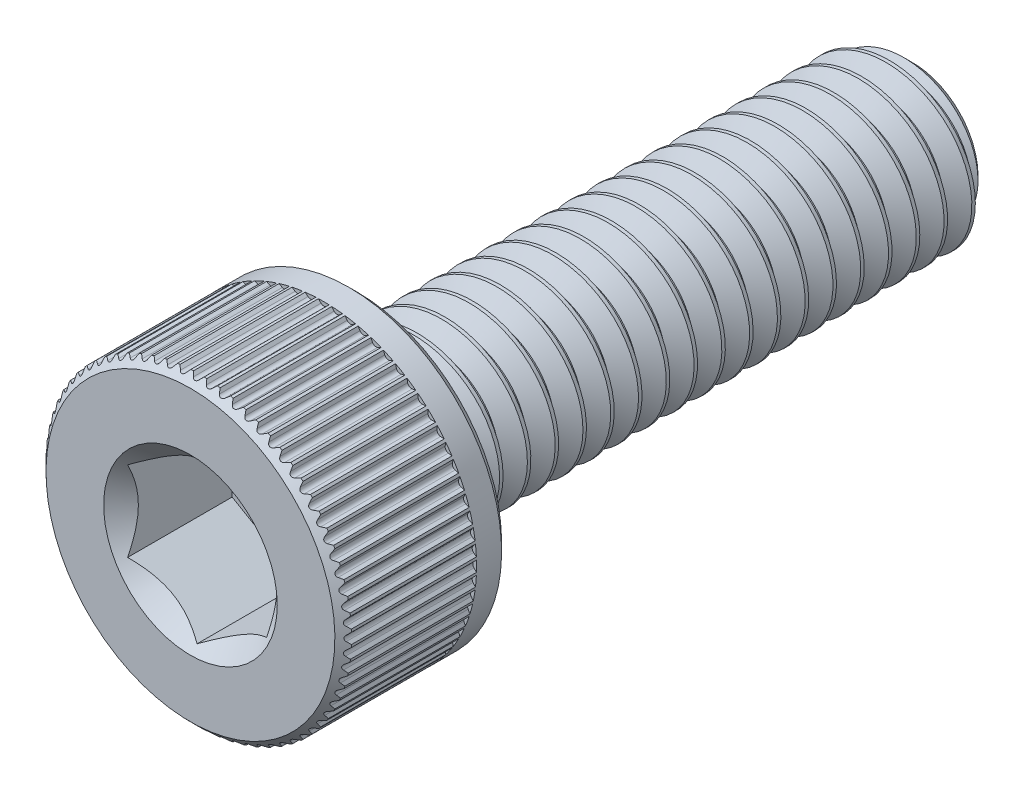
SolidWorks part; units mm, degrees
ref_plane "Front Plane" through (0, 0, 0) normal (0, 0, 1) x (1, 0, 0)
ref_plane "Top Plane" through (0, 0, 0) normal (0, 1, 0) x (1, 0, 0)
ref_plane "Right Plane" through (0, 0, 0) normal (1, 0, 0) x (0, 0, -1)
sketch "Sketch1" plane through (0, 0, 0) normal (1, 0, 0) x (0, 0, -1)
  line L0 (-6.5, 0) -> (6.5, 0) construction
  line L1 (6.5, 0) -> (6.5, 1.1752) construction
  line L2 (6.5, 1.1752) -> (6.1752, 1.5) construction
  line L3 (6.1752, 1.5) -> (6.125, 1.5) construction
  line L4 (6.125, 1.5) -> (-3.5, 1.5) construction
  line L5 (-3.5, 1.5) -> (-3.5, 2.75) construction
  line L6 (-3.5, 2.75) -> (-6.5, 2.75) construction
  line L7 (-6.5, 2.75) -> (-6.5, 0) construction
  line L8 (6.5, 1.1752) -> (6.5, 1.5) construction
  line L9 (6.4688, 1.5541) -> (6.7188, 1.1211) construction
  line L10 (6.7188, 1.1211) -> (6.9688, 1.5541) construction
  line L11 (6.9688, 1.5541) -> (6.4688, 1.5541) construction
  line L12 (6.7188, 1.5541) -> (6.7188, 1.5) construction
  line L13 (6.7188, 1.1211) -> (6.7188, 1.1752) construction
  line L14 (6.6875, 1.1752) -> (6.75, 1.1752) construction
  line L15 (6.5, 1.5) -> (6.9375, 1.5) construction
  line L16 (6.4844, 1.5271) -> (6.9531, 1.5271) construction
  line L17 (6.5, 0) -> (6.5, -1.5) construction
  line L18 (-3.65, 2.75) -> (-3.5, 2.6) construction
  line L19 (-6.35, 2.75) -> (-6.5, 2.6) construction
  line L20 (-3.5, 1.5) -> (-3.5, 0) construction
  line L21 (-3.5, 0.75) -> (-0.1667, 0.75) construction
  line L22 (-0.1667, 0.75) -> (3.1667, 0.75) construction
  line L23 (3.1667, 0.75) -> (6.5, 0.75) construction
  line L24 (-0.1667, 0.75) -> (-0.1667, 1.5) construction
  line L25 (-0.1667, 1.5) -> (-0.1667, 2.75) construction
  line L26 (3.1667, 0.75) -> (3.1667, 2.75) construction
  point P0 (-6.5, 1.25)
  point P3 (5.25, 1.5)
  point P4 (0, 0)
  point P18 (3.1667, 1.5)
  point P22 (6.7188, 1.1752)
  point P24 (6.125, 1.5)
  point P25 (6.7188, 1.5)
  point P28 (6.7188, 1.5271)
  point P29 (5.25, -1.5)
  point P30 (-0.1667, 1.5)
  point P31 (-5, 2.75)
  point P37 (-4.025, 2.75)
  point P38 (-6.275, 2.75)
  point P45 (-0.1667, 0.75)
  point P46 (3.1667, 0.75)
  dimension "D2" = 0.0625
  dimension "D7" = 0.15
  dimension "D8" = 0.15
  dimension "D9" = 0.15
  dimension "D10" = 0.075
  dimension "D11" = 0.375
  dimension "Drive Size" = 2.5
  dimension "Head Diameter" = 5.5
  dimension "Head Height" = 3
  dimension "Thread Pitch" = 0.5
  dimension "Thread Size" = 3
  dimension "Length" = 10
  dimension "D12" = 0.375
  dimension "D4" = 1.25
  dimension "D3" = 45
sketch "Sketch2" plane through (0, 0, 0) normal (1, 0, 0) x (0, 0, -1)
  line L0 (-6.5, 0) -> (-6.5, 2.6)
  line L1 (-6.35, 2.75) -> (-3.65, 2.75)
  line L2 (-3.5, 2.6) -> (-3.5, 1.65)
  line L4 (6.1752, 1.5) -> (6.5, 1.1752)
  line L5 (6.5, 1.1752) -> (6.5, 0)
  line L6 (-3.5, 2.75) -> (-6.5, 2.75) construction
  line L7 (6.5, 0) -> (-6.5, 0)
  line L8 (-6.35, 2.75) -> (-6.5, 2.6) construction
  line L10 (-6.35, 2.75) -> (-6.5, 2.6)
  line L14 (-3.65, 2.75) -> (-3.5, 2.6) construction
  line L16 (-3.65, 2.75) -> (-3.5, 2.6)
  line L17 (-3.5, 1.5) -> (-3.5, 2.75) construction
  line L19 (-3.35, 1.5) -> (6.1752, 1.5)
  line L20 (6.125, 1.5) -> (-3.5, 1.5) construction
  arc A1 (-3.5, 1.65) -> (-3.35, 1.5) centre (-3.35, 1.65) ccw
revolve "Revolve1" add sketch "Sketch2" angle 360 about L7
sketch "Sketch3" plane through (0, 0, 6.5) normal (0, 0, 1) x (1, 0, 0)
  line L1 (1.25, -0.7217) -> (1.25, 0.7217)
  line L2 (1.25, 0.7217) -> (0, 1.4434)
  line L3 (0, 1.4434) -> (-1.25, 0.7217)
  line L4 (-1.25, 0.7217) -> (-1.25, -0.7217)
  line L5 (-1.25, -0.7217) -> (0, -1.4434)
  line L6 (0, -1.4434) -> (1.25, -0.7217)
  circle A0 centre (0, 0) radius 1.25 construction
  circle A1 centre (0, 0) radius 2.75 construction
  circle A2 centre (0, 0) radius 2.75 construction
  circle A3 centre (0, 0) radius 1.4434 construction
  point P13 (0, 0)
extrude "Cut-Extrude1" cut sketch "Sketch3" against normal offset from surface (2 mm away) 1 up to face at (0, 2.6, 3.5)
sketch "Sketch4" plane through (0, 0, 6.5) normal (0, 0, 1) x (1, 0, 0)
  circle A0 centre (0, 0) radius 1.5625
  dimension "D1" = 3.125
extrude "Cut-Extrude2" cut sketch "Sketch4" against normal up to vertex (1.5 mm away) draft 45 up to point (0, 2.75, 5)
sketch "Sketch11" plane through (0, 0, 0) normal (1, 0, 0) x (0, 0, -1)
  line L0 (-6.5, 0) -> (6.5, 0) construction
  line L1 (-6.5, 0) -> (6.5, 0) construction
  line L2 (-1.625, 0) -> (-1.625, 1.5) construction
  line L3 (6.125, 1.5) -> (-3.5, 1.5) construction
  line L4 (4.625, 0) -> (4.625, 1.5) construction
  line L6 (6.5, 1.1752) -> (6.5, 1.5) construction
  point P2 (-1.625, 0)
  point P3 (4.625, 0)
  dimension "D1" = 1.875
  dimension "D2" = 1.875
sketch "Sketch6" plane through (0, 0, -6.5) normal (0, 0, -1) x (-1, 0, 0)
  circle A0 centre (0, 0) radius 1.5
curve "Helix/Spiral1" pitch 0.5 height 10.5 turns 21
sketch "Sketch10" plane through (0, 0, 0) normal (1, 0, 0) x (0, 0, -1)
  line L0 (-3.35, -2.75) -> (-3.35, 2.75)
  line L5 (-6.5, 0) -> (6.5, 0) construction
  line L6 (-3.35, 1.5) -> (-3.35, -1.5) construction
  point P3 (-3.35, 0)
split "Split1" trim tools "Sketch10" bodies to split 106 resulting bodies 114 115
sketch "Sketch7" plane through (0, 0, 0) normal (1, 0, 0) x (0, 0, -1)
  line L0 (6.4844, 1.5271) -> (6.9531, 1.5271)
  line L1 (6.9531, 1.5271) -> (6.75, 1.1752)
  line L2 (6.75, 1.1752) -> (6.6875, 1.1752)
  line L3 (6.6875, 1.1752) -> (6.4844, 1.5271)
sweep "Cut-Sweep1" cut profiles "Sketch7" path "Helix/Spiral1" align with end faces yes
sketch "Sketch8" plane through (0, 0, 0) normal (1, 0, 0) x (0, 0, -1)
  line L0 (-3.5, 0) -> (-3.5, 1.5)
  line L1 (-3.35, -1.5) -> (-3.35, 1.5) construction
  line L2 (-3.5, 1.5) -> (-3.35, 1.5)
  line L4 (-3.35, 1.5) -> (-2.484, 0)
  line L5 (-2.484, 0) -> (-3.5, 0)
  line L6 (6.125, 1.5) -> (-3.5, 1.5) construction
  line L7 (-6.5, 0) -> (6.5, 0) construction
  dimension "D1" = 60
revolve "Revolve2" add sketch "Sketch8" angle 360 about L5
ref_plane "Plane1" through (0, 0, 6.5) normal (0, 0, 1) x (1, 0, 0)
sketch "Sketch12" plane through (0, 0, 6.5) normal (0, 0, 1) x (1, 0, 0)
  line L0 (0, 0) -> (0.096, 2.7483) construction
  line L1 (0, 0) -> (-0.096, 2.7483) construction
  line L2 (0, 2.6812) -> (0, 2.8187) construction
  line L3 (-0.1664, 2.8187) -> (0.1664, 2.8187)
  line L4 (-0.1664, 2.8187) -> (-0.0493, 2.7017)
  line L5 (0.0493, 2.7017) -> (0.1664, 2.8187)
  circle A0 centre (0, 0) radius 2.75 construction
  arc A1 (-0.0493, 2.7017) -> (0.0493, 2.7017) centre (0, 2.751) ccw
  point P9 (0, 2.8187)
  point P13 (0, 2.75)
  dimension "D1" = 4
  dimension "D2" = 0.0688
extrude "Cut-Extrude3" cut sketch "Sketch12" against normal blind 2.4
pattern_circular "CirPattern1" count 72 over 360 about axis through (0, 0, 0) along (0, 0, 1) of "Cut-Extrude3"
equation "\"D2@Sketch1\" = \"Thread Pitch@Sketch1\" / 8"
equation "\"D4@Helix/Spiral1\" = \"Thread Pitch@Sketch1\""
equation "\"D7@Sketch1\" = \"Head Height@Sketch1\" * .05"
equation "\"D8@Sketch1\"=\"D7@Sketch1\""
equation "\"D9@Sketch1\"=\"D7@Sketch1\""
equation "\"D10@Sketch1\"=\"D7@Sketch1\"/2"
equation "\"D11@Sketch1\"=\"D10@Sketch1\"*5"
equation "\"D4@Sketch1\"=\"Thread Pitch@Sketch1\"*2.5"
equation "\"D12@Sketch1\"=\"Thread Pitch@Sketch1\"*.75"
equation "\"D3@Helix/Spiral1\"=\"Length@Sketch1\"+\"Thread Pitch@Sketch1\""
equation "\"D3@Sketch2\" = \"Thread Size@Sketch1\" * 0.05"
equation "\"D1@Sketch11\"=\"Length@Sketch1\"*0.1875"
equation "\"D2@Sketch11\"=\"D1@Sketch11\""
equation "\"D2@Sketch12\"=\"Head Diameter@Sketch1\"*.0125"
equation "\"D1@Cut-Extrude3\"=\"Head Height@Sketch1\"*.8"
equation "\"D1@CirPattern1\"=\"D3@CirPattern1\"/(1.25*\"D1@Sketch12\")"
equation "\"D1@Sketch4\"=\"Drive Size@Sketch1\"*1.25"
